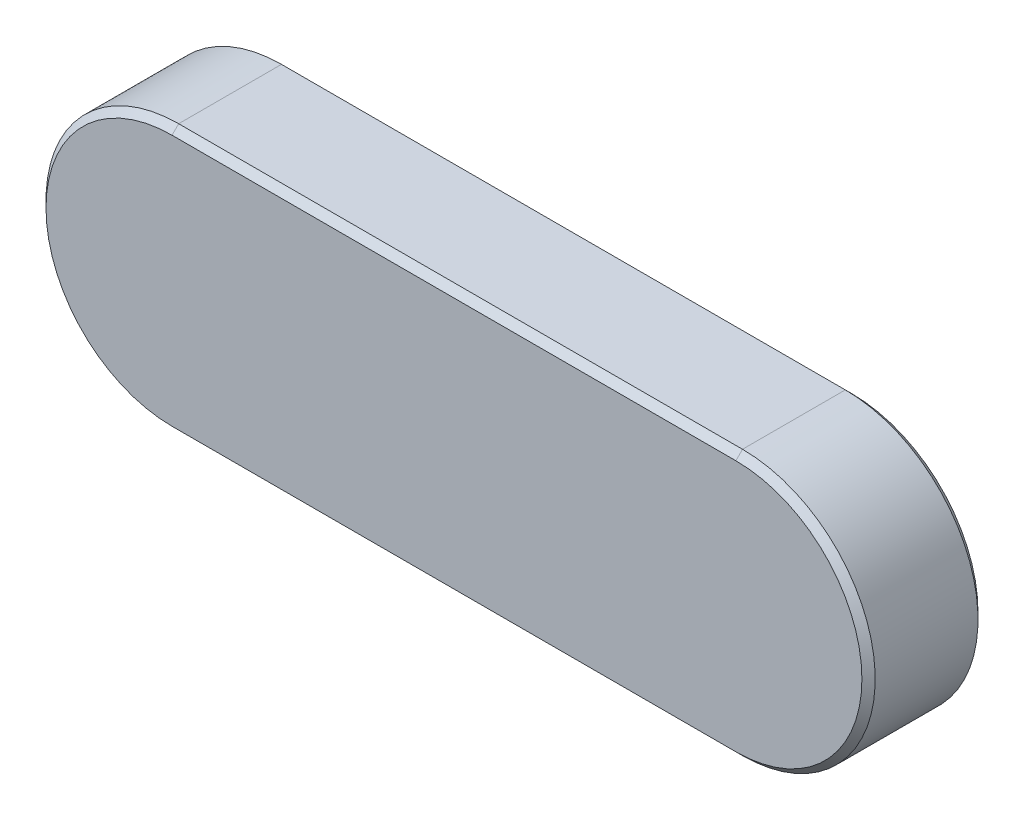
SolidWorks part; units mm, degrees
ref_plane "Front" through (0, 0, 0) normal (0, 0, 1) x (1, 0, 0)
ref_plane "Top" through (0, 0, 0) normal (0, 1, 0) x (1, 0, 0)
ref_plane "Right" through (0, 0, 0) normal (1, 0, 0) x (0, 0, -1)
sketch "Sketch1" plane through (0, 0, 0) normal (0, 0, 1) x (1, 0, 0)
  line L0 (-52.9374, 0) -> (56.5693, 0) construction
  line L1 (0, 11.4129) -> (0, -11.6476) construction
  line L3 (-17, 8) -> (17, 8)
  line L5 (-17, -8) -> (17, -8)
  arc A0 (17, 8) -> (17, -8) centre (17, 0) cw
  arc A1 (-17, 8) -> (-17, -8) centre (-17, 0) ccw
extrude "BaseKey" add sketch "Sketch1" along normal mid plane 7
sketch "Sketch2" plane through (0, 0, 0) normal (0, 0, 1) x (1, 0, 0)
  line L0 (-25, 8) -> (25, 8)
  line L1 (25, 8) -> (25, -8)
  line L2 (25, 0) -> (0, 0) construction
  line L3 (0, 0) -> (0, 8) construction
  line L4 (-25, -8) -> (25, -8)
  line L5 (-25, 8) -> (-25, -8)
  line L6 (-17, 8) -> (17, 8) construction
  point P8 (0, -8)
  dimension "D1" = 50
  dimension "D2" = 16
extrude "Extrude1" [suppressed] add sketch "Sketch2" along normal mid plane 7
sketch "Sketch3" plane through (0, 0, 0) normal (0, 0, 1) x (1, 0, 0)
  line L0 (-17, -8) -> (25, -8)
  line L1 (-17, 8) -> (25, 8)
  line L2 (25, 8) -> (25, -8)
  line L3 (-25, 0) -> (25, 0) construction
  arc A0 (17, -8) -> (17, 8) centre (17, 0) ccw construction
  arc A1 (-17, 8) -> (-17, -8) centre (-17, 0) ccw
  dimension "D1" = 16
  dimension "D2" = 50
extrude "Extrude2" [suppressed] add sketch "Sketch3" along normal mid plane
chamfer "Chamfer1" distance 0.4 angle 45 8 edges at (0, 8, 3.5) (0, 8, -3.5) (0, -8, -3.5) (0, -8, 3.5) (-25, 0, -3.5) (25, 0, -3.5) (-25, 0, 3.5) (25, 0, 3.5)
chamfer "Chamfer2" [suppressed] distance 0.4 angle 45
equation "\"D1@Sketch2\" = \"L@Sketch1\""
equation "\"D2@Sketch2\" = \"b@Sketch1\""
equation "\"D1@Extrude1\" = \"h@BaseKey\""
equation "\"D2@Sketch3\" = \"L@Sketch1\""
equation "\"D1@Sketch3\" = \"b@Sketch1\""
equation "\"D1@Extrude2\" = \"h@BaseKey\""
